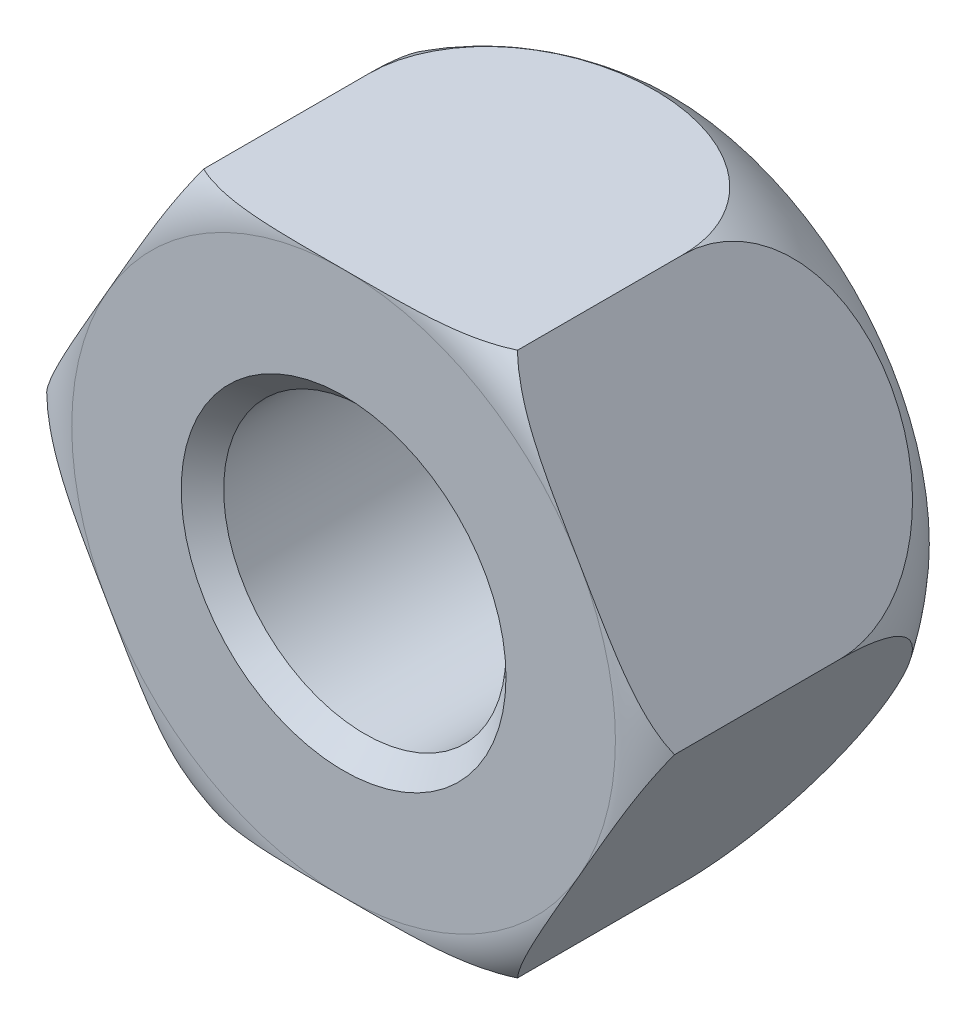
SolidWorks part; units mm, degrees
ref_plane "Front Plane" through (0, 0, 0) normal (0, 0, 1) x (1, 0, 0)
ref_plane "Top Plane" through (0, 0, 0) normal (0, 1, 0) x (1, 0, 0)
ref_plane "Right Plane" through (0, 0, 0) normal (1, 0, 0) x (0, 0, -1)
ref_axis "Axis_X" through (-88.99, 0, 0) along (1, 0, 0)
ref_axis "Axis_Y" through (0, 55, 0) along (0, -1, 0)
ref_axis "Axis_Z" through (0, 0, -88.99) along (0, 0, 1)
sketch "Sketch1" plane through (0, 0, 0) normal (0, 0, 1) x (1, 0, 0)
  line L1 (3.695, 6.4) -> (-3.695, 6.4)
  line L2 (-3.695, 6.4) -> (-7.3901, 0)
  line L3 (-7.3901, 0) -> (-3.695, -6.4)
  line L4 (-3.695, -6.4) -> (3.695, -6.4)
  line L5 (3.695, -6.4) -> (7.3901, 0)
  line L6 (7.3901, 0) -> (3.695, 6.4)
  circle A0 centre (0, 0) radius 6.4 construction
  circle A1 centre (0, 0) radius 3.3235
  dimension "HSD_1" = 6.647
  dimension "MSM_12" = 12.8
extrude "Boss-Extrude1" add sketch "Sketch1" against normal blind 7.7
cosmetic thread "Thread1" parameters "MSM_11"=8
sketch "Sketch2" plane through (0, 0, 0) normal (0, 1, 0) x (1, 0, 0)
  line L0 (-7.3901, 7.7) -> (-7.3901, 4.3)
  line L1 (-7.3901, 7.7) -> (-7.3901, 0) construction
  line L3 (-3.695, 7.7) -> (-7.3901, 7.7) construction
  line L4 (-6.0901, 7.7) -> (-7.3901, 7.7)
  line L5 (-7.3901, 0) -> (-7.3901, 0.4)
  line L7 (-3.695, 0) -> (-7.3901, 0) construction
  line L8 (-6.4, 0) -> (-7.3901, 0)
  arc A0 (-6.0901, 7.7) -> (-7.3901, 4.3) centre (-2.2939, 4.3) ccw
  arc A1 (-7.3901, 0.4) -> (-6.4, 0) centre (-6.4, 1.4253) ccw
  dimension "FIX_1" = 0.4
  dimension "FIX_2" = 3.4
  dimension "FIX_3" = 1.3
revolve "Cut-Revolve1" cut sketch "Sketch2" angle 360 about axis through (0, 0, -88.99) along (0, 0, 1)
chamfer "Chamfer1" distance 0.5 angle 45 2 edges at (3.3235, 0, -7.7) (3.3235, 0, 0)
equation "\"Factor\"= 1.082532"
